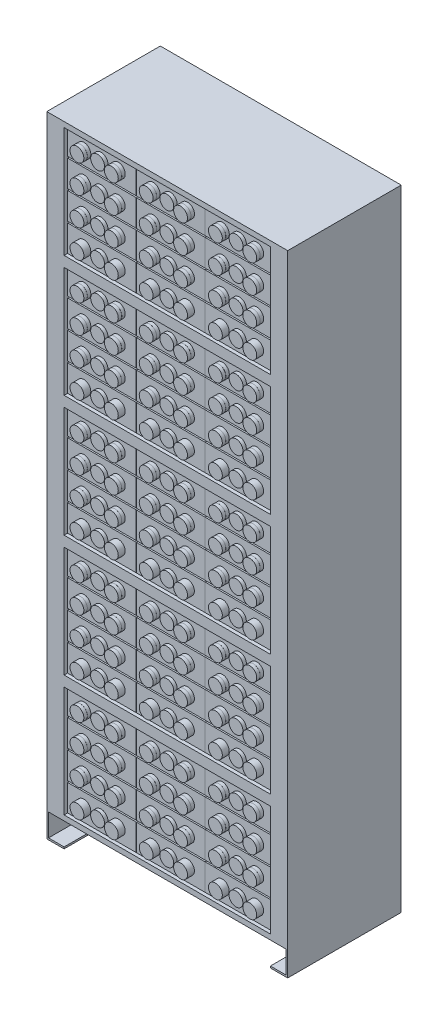
SolidWorks part; units mm, degrees
ref_plane "Front Plane" through (0, 0, 0) normal (0, 0, 1) x (1, 0, 0)
ref_plane "Top Plane" through (0, 0, 0) normal (0, 1, 0) x (1, 0, 0)
ref_plane "Right Plane" through (0, 0, 0) normal (1, 0, 0) x (0, 0, -1)
sketch "Sketch1" plane through (0, 0, 0) normal (0, 0, 1) x (1, 0, 0)
  line L0 (0, 0) -> (0, 1820)
  line L5 (0, 0) -> (50, 0)
  line L6 (696, 0) -> (696, 1820)
  line L7 (696, 1820) -> (0, 1820)
  line L8 (50, 0) -> (50, 5)
  line L10 (50, 755) -> (646, 755)
  line L11 (50, 435) -> (50, 755)
  line L12 (50, 435) -> (646, 435)
  line L14 (50, 85) -> (646, 85)
  line L15 (646, 435) -> (646, 755)
  line L16 (50, 1105) -> (646, 1105)
  line L17 (50, 85) -> (50, 405)
  line L18 (50, 405) -> (646, 405)
  line L19 (646, 85) -> (646, 405)
  line L20 (50, 785) -> (50, 1105)
  line L21 (50, 785) -> (646, 785)
  line L22 (646, 785) -> (646, 1105)
  line L23 (50, 1455) -> (646, 1455)
  line L24 (50, 1135) -> (50, 1455)
  line L25 (50, 1135) -> (646, 1135)
  line L26 (646, 1135) -> (646, 1455)
  line L27 (50, 1805) -> (646, 1805)
  line L28 (50, 1485) -> (50, 1805)
  line L29 (50, 1485) -> (646, 1485)
  line L30 (646, 1485) -> (646, 1805)
  line L31 (50, 5) -> (5, 5)
  line L32 (5, 5) -> (5, 70)
  line L33 (5, 70) -> (50, 70)
  line L34 (50, 70) -> (646, 70)
  line L36 (646, 0) -> (696, 0)
  line L37 (646, 0) -> (646, 5)
  line L39 (646, 5) -> (691, 5)
  line L40 (691, 5) -> (691, 70)
  line L41 (691, 70) -> (646, 70)
  dimension "D1" = 1820
  dimension "D2" = 696
  dimension "D3" = 320
  dimension "D4" = 5
  dimension "D5" = 596
  dimension "D6" = 15
  dimension "D7" = 15
  dimension "D8" = 70
  dimension "D9" = 5
  dimension "D10" = 5
  dimension "D11" = 596
  dimension "D12" = 45
  dimension "D13" = 65
  dimension "D14" = 5
  dimension "D15" = 45
  dimension "D16" = 50
extrude "Boss-Extrude1" add sketch "Sketch1" against normal blind 405
sketch "Sketch2" plane through (0, 0, -405) normal (0, 0, -1) x (-1, 0, 0)
  line L2 (-447.2, 161.3661) -> (-248.8, 161.3661)
  line L8 (-447.2, 511.3661) -> (-248.8, 511.3661)
  line L9 (-50, 434.5661) -> (-248.4, 434.5661)
  line L10 (-248.4, 434.5661) -> (-248.4, 511.3661)
  line L11 (-248.4, 511.3661) -> (-50, 511.3661)
  line L12 (-50, 511.3661) -> (-50, 434.5661)
  line L13 (-447.2, 434.5661) -> (-447.2, 511.3661)
  line L14 (-50, 84.5661) -> (-248.4, 84.5661)
  line L15 (-50, 405) -> (-50, 85) construction
  line L16 (-248.4, 84.5661) -> (-248.4, 161.3661)
  line L17 (-248.4, 161.3661) -> (-50, 161.3661)
  line L18 (-50, 161.3661) -> (-50, 84.5661)
  line L19 (-447.2, 84.5661) -> (-447.2, 161.3661)
  line L20 (-248.8, 84.5661) -> (-447.2, 84.5661)
  line L21 (-248.8, 161.3661) -> (-248.8, 84.5661)
  line L22 (-646, 161.3661) -> (-447.6, 161.3661)
  line L23 (-646, 84.5661) -> (-646, 161.3661)
  line L24 (-447.6, 84.5661) -> (-646, 84.5661)
  line L25 (-447.6, 161.3661) -> (-447.6, 84.5661)
  line L26 (-447.2, 242.5774) -> (-248.8, 242.5774)
  line L27 (-447.2, 165.7774) -> (-447.2, 242.5774)
  line L28 (-248.8, 165.7774) -> (-447.2, 165.7774)
  line L29 (-248.8, 242.5774) -> (-248.8, 165.7774)
  line L30 (-646, 242.5774) -> (-447.6, 242.5774)
  line L31 (-646, 165.7774) -> (-646, 242.5774)
  line L32 (-447.6, 165.7774) -> (-646, 165.7774)
  line L33 (-447.6, 242.5774) -> (-447.6, 165.7774)
  line L34 (-447.2, 323.7887) -> (-248.8, 323.7887)
  line L35 (-447.2, 246.9887) -> (-447.2, 323.7887)
  line L36 (-248.8, 246.9887) -> (-447.2, 246.9887)
  line L37 (-248.8, 323.7887) -> (-248.8, 246.9887)
  line L38 (-646, 323.7887) -> (-447.6, 323.7887)
  line L39 (-646, 246.9887) -> (-646, 323.7887)
  line L40 (-447.6, 246.9887) -> (-646, 246.9887)
  line L41 (-447.6, 323.7887) -> (-447.6, 246.9887)
  line L42 (-447.2, 405) -> (-248.8, 405)
  line L43 (-447.2, 328.2) -> (-447.2, 405)
  line L44 (-248.8, 328.2) -> (-447.2, 328.2)
  line L45 (-248.8, 405) -> (-248.8, 328.2)
  line L46 (-646, 405) -> (-447.6, 405)
  line L47 (-646, 328.2) -> (-646, 405)
  line L48 (-447.6, 328.2) -> (-646, 328.2)
  line L49 (-447.6, 405) -> (-447.6, 328.2)
  line L50 (-248.4, 242.5774) -> (-50, 242.5774)
  line L51 (-248.4, 165.7774) -> (-248.4, 242.5774)
  line L52 (-50, 165.7774) -> (-248.4, 165.7774)
  line L53 (-50, 242.5774) -> (-50, 165.7774)
  line L54 (-248.4, 323.7887) -> (-50, 323.7887)
  line L55 (-248.4, 246.9887) -> (-248.4, 323.7887)
  line L56 (-50, 246.9887) -> (-248.4, 246.9887)
  line L57 (-50, 323.7887) -> (-50, 246.9887)
  line L58 (-248.4, 405) -> (-50, 405)
  line L59 (-248.4, 328.2) -> (-248.4, 405)
  line L60 (-50, 328.2) -> (-248.4, 328.2)
  line L61 (-50, 405) -> (-50, 328.2)
  line L62 (-248.8, 434.5661) -> (-447.2, 434.5661)
  line L63 (-248.8, 511.3661) -> (-248.8, 434.5661)
  line L64 (-646, 511.3661) -> (-447.6, 511.3661)
  line L65 (-646, 434.5661) -> (-646, 511.3661)
  line L66 (-447.6, 434.5661) -> (-646, 434.5661)
  line L67 (-447.6, 511.3661) -> (-447.6, 434.5661)
  line L68 (-447.2, 592.5774) -> (-248.8, 592.5774)
  line L69 (-447.2, 515.7774) -> (-447.2, 592.5774)
  line L70 (-248.8, 515.7774) -> (-447.2, 515.7774)
  line L71 (-248.8, 592.5774) -> (-248.8, 515.7774)
  line L72 (-646, 592.5774) -> (-447.6, 592.5774)
  line L73 (-646, 515.7774) -> (-646, 592.5774)
  line L74 (-447.6, 515.7774) -> (-646, 515.7774)
  line L75 (-447.6, 592.5774) -> (-447.6, 515.7774)
  line L76 (-447.2, 673.7887) -> (-248.8, 673.7887)
  line L77 (-447.2, 596.9887) -> (-447.2, 673.7887)
  line L78 (-248.8, 596.9887) -> (-447.2, 596.9887)
  line L79 (-248.8, 673.7887) -> (-248.8, 596.9887)
  line L80 (-646, 673.7887) -> (-447.6, 673.7887)
  line L81 (-646, 596.9887) -> (-646, 673.7887)
  line L82 (-447.6, 596.9887) -> (-646, 596.9887)
  line L83 (-447.6, 673.7887) -> (-447.6, 596.9887)
  line L84 (-447.2, 755) -> (-248.8, 755)
  line L85 (-447.2, 678.2) -> (-447.2, 755)
  line L86 (-248.8, 678.2) -> (-447.2, 678.2)
  line L87 (-248.8, 755) -> (-248.8, 678.2)
  line L88 (-646, 755) -> (-447.6, 755)
  line L89 (-646, 678.2) -> (-646, 755)
  line L90 (-447.6, 678.2) -> (-646, 678.2)
  line L91 (-447.6, 755) -> (-447.6, 678.2)
  line L92 (-248.4, 592.5774) -> (-50, 592.5774)
  line L93 (-248.4, 515.7774) -> (-248.4, 592.5774)
  line L94 (-50, 515.7774) -> (-248.4, 515.7774)
  line L95 (-50, 592.5774) -> (-50, 515.7774)
  line L96 (-248.4, 673.7887) -> (-50, 673.7887)
  line L97 (-248.4, 596.9887) -> (-248.4, 673.7887)
  line L98 (-50, 596.9887) -> (-248.4, 596.9887)
  line L99 (-50, 673.7887) -> (-50, 596.9887)
  line L100 (-248.4, 755) -> (-50, 755)
  line L101 (-248.4, 678.2) -> (-248.4, 755)
  line L102 (-50, 678.2) -> (-248.4, 678.2)
  line L103 (-50, 755) -> (-50, 678.2)
  line L104 (-447.2, 861.3661) -> (-248.8, 861.3661)
  line L105 (-50, 784.5661) -> (-248.4, 784.5661)
  line L106 (-248.4, 784.5661) -> (-248.4, 861.3661)
  line L107 (-248.4, 861.3661) -> (-50, 861.3661)
  line L108 (-50, 861.3661) -> (-50, 784.5661)
  line L109 (-447.2, 784.5661) -> (-447.2, 861.3661)
  line L110 (-248.8, 784.5661) -> (-447.2, 784.5661)
  line L111 (-248.8, 861.3661) -> (-248.8, 784.5661)
  line L112 (-646, 861.3661) -> (-447.6, 861.3661)
  line L113 (-646, 784.5661) -> (-646, 861.3661)
  line L114 (-447.6, 784.5661) -> (-646, 784.5661)
  line L115 (-447.6, 861.3661) -> (-447.6, 784.5661)
  line L116 (-447.2, 942.5774) -> (-248.8, 942.5774)
  line L117 (-447.2, 865.7774) -> (-447.2, 942.5774)
  line L118 (-248.8, 865.7774) -> (-447.2, 865.7774)
  line L119 (-248.8, 942.5774) -> (-248.8, 865.7774)
  line L120 (-646, 942.5774) -> (-447.6, 942.5774)
  line L121 (-646, 865.7774) -> (-646, 942.5774)
  line L122 (-447.6, 865.7774) -> (-646, 865.7774)
  line L123 (-447.6, 942.5774) -> (-447.6, 865.7774)
  line L124 (-447.2, 1023.7887) -> (-248.8, 1023.7887)
  line L125 (-447.2, 946.9887) -> (-447.2, 1023.7887)
  line L126 (-248.8, 946.9887) -> (-447.2, 946.9887)
  line L127 (-248.8, 1023.7887) -> (-248.8, 946.9887)
  line L128 (-646, 1023.7887) -> (-447.6, 1023.7887)
  line L129 (-646, 946.9887) -> (-646, 1023.7887)
  line L130 (-447.6, 946.9887) -> (-646, 946.9887)
  line L131 (-447.6, 1023.7887) -> (-447.6, 946.9887)
  line L132 (-447.2, 1105) -> (-248.8, 1105)
  line L133 (-447.2, 1028.2) -> (-447.2, 1105)
  line L134 (-248.8, 1028.2) -> (-447.2, 1028.2)
  line L135 (-248.8, 1105) -> (-248.8, 1028.2)
  line L136 (-646, 1105) -> (-447.6, 1105)
  line L137 (-646, 1028.2) -> (-646, 1105)
  line L138 (-447.6, 1028.2) -> (-646, 1028.2)
  line L139 (-447.6, 1105) -> (-447.6, 1028.2)
  line L140 (-248.4, 942.5774) -> (-50, 942.5774)
  line L141 (-248.4, 865.7774) -> (-248.4, 942.5774)
  line L142 (-50, 865.7774) -> (-248.4, 865.7774)
  line L143 (-50, 942.5774) -> (-50, 865.7774)
  line L144 (-248.4, 1023.7887) -> (-50, 1023.7887)
  line L145 (-248.4, 946.9887) -> (-248.4, 1023.7887)
  line L146 (-50, 946.9887) -> (-248.4, 946.9887)
  line L147 (-50, 1023.7887) -> (-50, 946.9887)
  line L148 (-248.4, 1105) -> (-50, 1105)
  line L149 (-248.4, 1028.2) -> (-248.4, 1105)
  line L150 (-50, 1028.2) -> (-248.4, 1028.2)
  line L151 (-50, 1105) -> (-50, 1028.2)
  line L152 (-447.2, 1211.3661) -> (-248.8, 1211.3661)
  line L153 (-50, 1134.5661) -> (-248.4, 1134.5661)
  line L154 (-248.4, 1134.5661) -> (-248.4, 1211.3661)
  line L155 (-248.4, 1211.3661) -> (-50, 1211.3661)
  line L156 (-50, 1211.3661) -> (-50, 1134.5661)
  line L157 (-447.2, 1134.5661) -> (-447.2, 1211.3661)
  line L158 (-248.8, 1134.5661) -> (-447.2, 1134.5661)
  line L159 (-248.8, 1211.3661) -> (-248.8, 1134.5661)
  line L160 (-646, 1211.3661) -> (-447.6, 1211.3661)
  line L161 (-646, 1134.5661) -> (-646, 1211.3661)
  line L162 (-447.6, 1134.5661) -> (-646, 1134.5661)
  line L163 (-447.6, 1211.3661) -> (-447.6, 1134.5661)
  line L164 (-447.2, 1292.5774) -> (-248.8, 1292.5774)
  line L165 (-447.2, 1215.7774) -> (-447.2, 1292.5774)
  line L166 (-248.8, 1215.7774) -> (-447.2, 1215.7774)
  line L167 (-248.8, 1292.5774) -> (-248.8, 1215.7774)
  line L168 (-646, 1292.5774) -> (-447.6, 1292.5774)
  line L169 (-646, 1215.7774) -> (-646, 1292.5774)
  line L170 (-447.6, 1215.7774) -> (-646, 1215.7774)
  line L171 (-447.6, 1292.5774) -> (-447.6, 1215.7774)
  line L172 (-447.2, 1373.7887) -> (-248.8, 1373.7887)
  line L173 (-447.2, 1296.9887) -> (-447.2, 1373.7887)
  line L174 (-248.8, 1296.9887) -> (-447.2, 1296.9887)
  line L175 (-248.8, 1373.7887) -> (-248.8, 1296.9887)
  line L176 (-646, 1373.7887) -> (-447.6, 1373.7887)
  line L177 (-646, 1296.9887) -> (-646, 1373.7887)
  line L178 (-447.6, 1296.9887) -> (-646, 1296.9887)
  line L179 (-447.6, 1373.7887) -> (-447.6, 1296.9887)
  line L180 (-447.2, 1455) -> (-248.8, 1455)
  line L181 (-447.2, 1378.2) -> (-447.2, 1455)
  line L182 (-248.8, 1378.2) -> (-447.2, 1378.2)
  line L183 (-248.8, 1455) -> (-248.8, 1378.2)
  line L184 (-646, 1455) -> (-447.6, 1455)
  line L185 (-646, 1378.2) -> (-646, 1455)
  line L186 (-447.6, 1378.2) -> (-646, 1378.2)
  line L187 (-447.6, 1455) -> (-447.6, 1378.2)
  line L188 (-248.4, 1292.5774) -> (-50, 1292.5774)
  line L189 (-248.4, 1215.7774) -> (-248.4, 1292.5774)
  line L190 (-50, 1215.7774) -> (-248.4, 1215.7774)
  line L191 (-50, 1292.5774) -> (-50, 1215.7774)
  line L192 (-248.4, 1373.7887) -> (-50, 1373.7887)
  line L193 (-248.4, 1296.9887) -> (-248.4, 1373.7887)
  line L194 (-50, 1296.9887) -> (-248.4, 1296.9887)
  line L195 (-50, 1373.7887) -> (-50, 1296.9887)
  line L196 (-248.4, 1455) -> (-50, 1455)
  line L197 (-248.4, 1378.2) -> (-248.4, 1455)
  line L198 (-50, 1378.2) -> (-248.4, 1378.2)
  line L199 (-50, 1455) -> (-50, 1378.2)
  line L200 (-447.2, 1561.3661) -> (-248.8, 1561.3661)
  line L201 (-50, 1484.5661) -> (-248.4, 1484.5661)
  line L202 (-248.4, 1484.5661) -> (-248.4, 1561.3661)
  line L203 (-248.4, 1561.3661) -> (-50, 1561.3661)
  line L204 (-50, 1561.3661) -> (-50, 1484.5661)
  line L205 (-447.2, 1484.5661) -> (-447.2, 1561.3661)
  line L206 (-248.8, 1484.5661) -> (-447.2, 1484.5661)
  line L207 (-248.8, 1561.3661) -> (-248.8, 1484.5661)
  line L208 (-646, 1561.3661) -> (-447.6, 1561.3661)
  line L209 (-646, 1484.5661) -> (-646, 1561.3661)
  line L210 (-447.6, 1484.5661) -> (-646, 1484.5661)
  line L211 (-447.6, 1561.3661) -> (-447.6, 1484.5661)
  line L212 (-447.2, 1642.5774) -> (-248.8, 1642.5774)
  line L213 (-447.2, 1565.7774) -> (-447.2, 1642.5774)
  line L214 (-248.8, 1565.7774) -> (-447.2, 1565.7774)
  line L215 (-248.8, 1642.5774) -> (-248.8, 1565.7774)
  line L216 (-646, 1642.5774) -> (-447.6, 1642.5774)
  line L217 (-646, 1565.7774) -> (-646, 1642.5774)
  line L218 (-447.6, 1565.7774) -> (-646, 1565.7774)
  line L219 (-447.6, 1642.5774) -> (-447.6, 1565.7774)
  line L220 (-447.2, 1723.7887) -> (-248.8, 1723.7887)
  line L221 (-447.2, 1646.9887) -> (-447.2, 1723.7887)
  line L222 (-248.8, 1646.9887) -> (-447.2, 1646.9887)
  line L223 (-248.8, 1723.7887) -> (-248.8, 1646.9887)
  line L224 (-646, 1723.7887) -> (-447.6, 1723.7887)
  line L225 (-646, 1646.9887) -> (-646, 1723.7887)
  line L226 (-447.6, 1646.9887) -> (-646, 1646.9887)
  line L227 (-447.6, 1723.7887) -> (-447.6, 1646.9887)
  line L228 (-447.2, 1805) -> (-248.8, 1805)
  line L229 (-447.2, 1728.2) -> (-447.2, 1805)
  line L230 (-248.8, 1728.2) -> (-447.2, 1728.2)
  line L231 (-248.8, 1805) -> (-248.8, 1728.2)
  line L232 (-646, 1805) -> (-447.6, 1805)
  line L233 (-646, 1728.2) -> (-646, 1805)
  line L234 (-447.6, 1728.2) -> (-646, 1728.2)
  line L235 (-447.6, 1805) -> (-447.6, 1728.2)
  line L236 (-248.4, 1642.5774) -> (-50, 1642.5774)
  line L237 (-248.4, 1565.7774) -> (-248.4, 1642.5774)
  line L238 (-50, 1565.7774) -> (-248.4, 1565.7774)
  line L239 (-50, 1642.5774) -> (-50, 1565.7774)
  line L240 (-248.4, 1723.7887) -> (-50, 1723.7887)
  line L241 (-248.4, 1646.9887) -> (-248.4, 1723.7887)
  line L242 (-50, 1646.9887) -> (-248.4, 1646.9887)
  line L243 (-50, 1723.7887) -> (-50, 1646.9887)
  line L244 (-248.4, 1805) -> (-50, 1805)
  line L245 (-248.4, 1728.2) -> (-248.4, 1805)
  line L246 (-50, 1728.2) -> (-248.4, 1728.2)
  line L247 (-50, 1805) -> (-50, 1728.2)
  line L248 (-646, 1805) -> (-50, 1805) construction
  dimension "D1" = 198.4
  dimension "D2" = 3
  dimension "D4" = 5
  dimension "D5" = 76.8
  dimension "D3" = 4
extrude "Boss-Extrude2" add sketch "Sketch2" against normal blind 318
sketch "Sketch3" plane through (0, 0, -87) normal (0, 0, 1) x (1, 0, 0)
  line L0 (447.6, 85) -> (447.6, 161.3661) construction
  line L1 (526.6, 123.183) -> (566.6, 123.183) construction
  line L2 (546.8, 161.3661) -> (546.8, 85) construction
  line L3 (646, 85) -> (447.6, 85) construction
  line L4 (447.6, 85) -> (447.6, 161.3661) construction
  line L5 (546.6, 123.183) -> (447.6, 123.183) construction
  line L6 (447.6, 1805) -> (646, 1805) construction
  line L7 (447.6, 1805) -> (646, 1805) construction
  line L8 (546.8, 405) -> (546.8, 328.2) construction
  line L9 (646, 328.2) -> (447.6, 328.2) construction
  line L10 (546.8, 1805) -> (546.8, 1728.2) construction
  line L11 (646, 1728.2) -> (447.6, 1728.2) construction
  line L12 (646, 1766.6) -> (447.6, 1766.6) construction
  line L13 (646, 1805) -> (646, 1728.2) construction
  line L14 (447.6, 1728.2) -> (447.6, 1805) construction
  circle A0 centre (546.6, 123.183) radius 20
  circle A1 centre (497.1, 123.183) radius 20
  circle A2 centre (596.5, 123.183) radius 20
  circle A3 centre (297.1, 123.183) radius 20
  circle A4 centre (346.6, 123.183) radius 20
  circle A5 centre (396.5, 123.183) radius 20
  circle A6 centre (97.1, 123.183) radius 20
  circle A7 centre (146.6, 123.183) radius 20
  circle A8 centre (196.5, 123.183) radius 20
  circle A9 centre (297.1667, 204.322) radius 20
  circle A10 centre (346.6667, 204.322) radius 20
  circle A11 centre (396.5667, 204.322) radius 20
  circle A12 centre (97.1667, 204.322) radius 20
  circle A13 centre (146.6667, 204.322) radius 20
  circle A14 centre (196.5667, 204.322) radius 20
  circle A15 centre (297.2333, 285.461) radius 20
  circle A16 centre (346.7333, 285.461) radius 20
  circle A17 centre (396.6333, 285.461) radius 20
  circle A18 centre (97.2333, 285.461) radius 20
  circle A19 centre (146.7333, 285.461) radius 20
  circle A20 centre (196.6333, 285.461) radius 20
  circle A21 centre (297.3, 366.6) radius 20
  circle A22 centre (346.8, 366.6) radius 20
  circle A23 centre (396.7, 366.6) radius 20
  circle A24 centre (97.3, 366.6) radius 20
  circle A25 centre (146.8, 366.6) radius 20
  circle A26 centre (196.7, 366.6) radius 20
  circle A27 centre (497.1667, 204.322) radius 20
  circle A28 centre (546.6667, 204.322) radius 20
  circle A29 centre (596.5667, 204.322) radius 20
  circle A30 centre (497.2333, 285.461) radius 20
  circle A31 centre (546.7333, 285.461) radius 20
  circle A32 centre (596.6333, 285.461) radius 20
  circle A33 centre (497.3, 366.6) radius 20
  circle A34 centre (546.8, 366.6) radius 20
  circle A35 centre (596.7, 366.6) radius 20
  circle A36 centre (546.6, 473.183) radius 20
  circle A37 centre (497.1, 473.183) radius 20
  circle A38 centre (596.5, 473.183) radius 20
  circle A39 centre (297.1, 473.183) radius 20
  circle A40 centre (346.6, 473.183) radius 20
  circle A41 centre (396.5, 473.183) radius 20
  circle A42 centre (97.1, 473.183) radius 20
  circle A43 centre (146.6, 473.183) radius 20
  circle A44 centre (196.5, 473.183) radius 20
  circle A45 centre (297.1667, 554.322) radius 20
  circle A46 centre (346.6667, 554.322) radius 20
  circle A47 centre (396.5667, 554.322) radius 20
  circle A48 centre (97.1667, 554.322) radius 20
  circle A49 centre (146.6667, 554.322) radius 20
  circle A50 centre (196.5667, 554.322) radius 20
  circle A51 centre (297.2333, 635.461) radius 20
  circle A52 centre (346.7333, 635.461) radius 20
  circle A53 centre (396.6333, 635.461) radius 20
  circle A54 centre (97.2333, 635.461) radius 20
  circle A55 centre (146.7333, 635.461) radius 20
  circle A56 centre (196.6333, 635.461) radius 20
  circle A57 centre (297.3, 716.6) radius 20
  circle A58 centre (346.8, 716.6) radius 20
  circle A59 centre (396.7, 716.6) radius 20
  circle A60 centre (97.3, 716.6) radius 20
  circle A61 centre (146.8, 716.6) radius 20
  circle A62 centre (196.7, 716.6) radius 20
  circle A63 centre (497.1667, 554.322) radius 20
  circle A64 centre (546.6667, 554.322) radius 20
  circle A65 centre (596.5667, 554.322) radius 20
  circle A66 centre (497.2333, 635.461) radius 20
  circle A67 centre (546.7333, 635.461) radius 20
  circle A68 centre (596.6333, 635.461) radius 20
  circle A69 centre (497.3, 716.6) radius 20
  circle A70 centre (546.8, 716.6) radius 20
  circle A71 centre (596.7, 716.6) radius 20
  circle A72 centre (546.6, 823.183) radius 20
  circle A73 centre (497.1, 823.183) radius 20
  circle A74 centre (596.5, 823.183) radius 20
  circle A75 centre (297.1, 823.183) radius 20
  circle A76 centre (346.6, 823.183) radius 20
  circle A77 centre (396.5, 823.183) radius 20
  circle A78 centre (97.1, 823.183) radius 20
  circle A79 centre (146.6, 823.183) radius 20
  circle A80 centre (196.5, 823.183) radius 20
  circle A81 centre (297.1667, 904.322) radius 20
  circle A82 centre (346.6667, 904.322) radius 20
  circle A83 centre (396.5667, 904.322) radius 20
  circle A84 centre (97.1667, 904.322) radius 20
  circle A85 centre (146.6667, 904.322) radius 20
  circle A86 centre (196.5667, 904.322) radius 20
  circle A87 centre (297.2333, 985.461) radius 20
  circle A88 centre (346.7333, 985.461) radius 20
  circle A89 centre (396.6333, 985.461) radius 20
  circle A90 centre (97.2333, 985.461) radius 20
  circle A91 centre (146.7333, 985.461) radius 20
  circle A92 centre (196.6333, 985.461) radius 20
  circle A93 centre (297.3, 1066.6) radius 20
  circle A94 centre (346.8, 1066.6) radius 20
  circle A95 centre (396.7, 1066.6) radius 20
  circle A96 centre (97.3, 1066.6) radius 20
  circle A97 centre (146.8, 1066.6) radius 20
  circle A98 centre (196.7, 1066.6) radius 20
  circle A99 centre (497.1667, 904.322) radius 20
  circle A100 centre (546.6667, 904.322) radius 20
  circle A101 centre (596.5667, 904.322) radius 20
  circle A102 centre (497.2333, 985.461) radius 20
  circle A103 centre (546.7333, 985.461) radius 20
  circle A104 centre (596.6333, 985.461) radius 20
  circle A105 centre (497.3, 1066.6) radius 20
  circle A106 centre (546.8, 1066.6) radius 20
  circle A107 centre (596.7, 1066.6) radius 20
  circle A108 centre (546.6, 1173.183) radius 20
  circle A109 centre (497.1, 1173.183) radius 20
  circle A110 centre (596.5, 1173.183) radius 20
  circle A111 centre (297.1, 1173.183) radius 20
  circle A112 centre (346.6, 1173.183) radius 20
  circle A113 centre (396.5, 1173.183) radius 20
  circle A114 centre (97.1, 1173.183) radius 20
  circle A115 centre (146.6, 1173.183) radius 20
  circle A116 centre (196.5, 1173.183) radius 20
  circle A117 centre (297.1667, 1254.322) radius 20
  circle A118 centre (346.6667, 1254.322) radius 20
  circle A119 centre (396.5667, 1254.322) radius 20
  circle A120 centre (97.1667, 1254.322) radius 20
  circle A121 centre (146.6667, 1254.322) radius 20
  circle A122 centre (196.5667, 1254.322) radius 20
  circle A123 centre (297.2333, 1335.461) radius 20
  circle A124 centre (346.7333, 1335.461) radius 20
  circle A125 centre (396.6333, 1335.461) radius 20
  circle A126 centre (97.2333, 1335.461) radius 20
  circle A127 centre (146.7333, 1335.461) radius 20
  circle A128 centre (196.6333, 1335.461) radius 20
  circle A129 centre (297.3, 1416.6) radius 20
  circle A130 centre (346.8, 1416.6) radius 20
  circle A131 centre (396.7, 1416.6) radius 20
  circle A132 centre (97.3, 1416.6) radius 20
  circle A133 centre (146.8, 1416.6) radius 20
  circle A134 centre (196.7, 1416.6) radius 20
  circle A135 centre (497.1667, 1254.322) radius 20
  circle A136 centre (546.6667, 1254.322) radius 20
  circle A137 centre (596.5667, 1254.322) radius 20
  circle A138 centre (497.2333, 1335.461) radius 20
  circle A139 centre (546.7333, 1335.461) radius 20
  circle A140 centre (596.6333, 1335.461) radius 20
  circle A141 centre (497.3, 1416.6) radius 20
  circle A142 centre (546.8, 1416.6) radius 20
  circle A143 centre (596.7, 1416.6) radius 20
  circle A144 centre (546.6, 1523.183) radius 20
  circle A145 centre (497.1, 1523.183) radius 20
  circle A146 centre (596.5, 1523.183) radius 20
  circle A147 centre (297.1, 1523.183) radius 20
  circle A148 centre (346.6, 1523.183) radius 20
  circle A149 centre (396.5, 1523.183) radius 20
  circle A150 centre (97.1, 1523.183) radius 20
  circle A151 centre (146.6, 1523.183) radius 20
  circle A152 centre (196.5, 1523.183) radius 20
  circle A153 centre (297.1667, 1604.322) radius 20
  circle A154 centre (346.6667, 1604.322) radius 20
  circle A155 centre (396.5667, 1604.322) radius 20
  circle A156 centre (97.1667, 1604.322) radius 20
  circle A157 centre (146.6667, 1604.322) radius 20
  circle A158 centre (196.5667, 1604.322) radius 20
  circle A159 centre (297.2333, 1685.461) radius 20
  circle A160 centre (346.7333, 1685.461) radius 20
  circle A161 centre (396.6333, 1685.461) radius 20
  circle A162 centre (97.2333, 1685.461) radius 20
  circle A163 centre (146.7333, 1685.461) radius 20
  circle A164 centre (196.6333, 1685.461) radius 20
  circle A165 centre (297.3, 1766.6) radius 20
  circle A166 centre (346.8, 1766.6) radius 20
  circle A167 centre (396.7, 1766.6) radius 20
  circle A168 centre (97.3, 1766.6) radius 20
  circle A169 centre (146.8, 1766.6) radius 20
  circle A170 centre (196.7, 1766.6) radius 20
  circle A171 centre (497.1667, 1604.322) radius 20
  circle A172 centre (546.6667, 1604.322) radius 20
  circle A173 centre (596.5667, 1604.322) radius 20
  circle A174 centre (497.2333, 1685.461) radius 20
  circle A175 centre (546.7333, 1685.461) radius 20
  circle A176 centre (596.6333, 1685.461) radius 20
  circle A177 centre (497.3, 1766.6) radius 20
  circle A178 centre (546.8, 1766.6) radius 20
  circle A179 centre (596.7, 1766.6) radius 20
  point P388 (546.8, 1766.6)
  dimension "D1" = 40
  dimension "D2" = 40
  dimension "D5" = 5
  dimension "D3" = 3
  dimension "D4" = 4
extrude "Boss-Extrude3" add sketch "Sketch3" along normal blind 10
sketch "Sketch4" plane through (0, 0, 0) normal (0, 0, 1) x (1, 0, 0)
  line L12 (0, 0) -> (50, 0)
  line L13 (50, 0) -> (50, 5)
  line L14 (50, 5) -> (5, 5)
  line L15 (5, 5) -> (5, 70)
  line L16 (5, 70) -> (691, 70)
  line L17 (691, 70) -> (691, 5)
  line L18 (691, 5) -> (646, 5)
  line L19 (646, 5) -> (646, 0)
  line L20 (646, 0) -> (696, 0)
  line L21 (696, 0) -> (696, 1820)
  line L22 (696, 1820) -> (0, 1820)
  line L23 (0, 1820) -> (0, 0)
  line L24 (0, 0) -> (50, 0)
  line L25 (50, 0) -> (50, 5)
  line L26 (50, 5) -> (5, 5)
  line L27 (5, 5) -> (5, 70)
  line L28 (5, 70) -> (691, 70)
  line L29 (691, 70) -> (691, 5)
  line L30 (691, 5) -> (646, 5)
  line L31 (646, 5) -> (646, 0)
  line L32 (646, 0) -> (696, 0)
  line L33 (696, 0) -> (696, 1820)
  line L34 (696, 1820) -> (0, 1820)
  line L35 (0, 1820) -> (0, 0)
  dimension "D1" = 0
extrude "Cut-Extrude1" cut sketch "Sketch4" against normal up to surface (77 mm away) up to face at (317.1667, 1604.322, -77)
sketch "Sketch5" plane through (0, 0, -77) normal (0, 0, 1) x (1, 0, 0)
  circle A0 centre (596.5, 123.183) radius 20 construction
  circle A1 centre (596.5, 123.183) radius 20
  circle A2 centre (497.1, 123.183) radius 20 construction
  circle A3 centre (497.1, 123.183) radius 20
  circle A4 centre (297.1, 123.183) radius 20 construction
  circle A5 centre (297.1, 123.183) radius 20
  circle A6 centre (196.5, 123.183) radius 20 construction
  circle A7 centre (97.1, 123.183) radius 20 construction
  circle A8 centre (396.5, 123.183) radius 20 construction
  circle A9 centre (196.5, 123.183) radius 20
  circle A10 centre (97.1, 123.183) radius 20
  circle A11 centre (396.5, 123.183) radius 20
  circle A12 centre (97.1, 204.322) radius 20
  circle A13 centre (196.5, 204.322) radius 20
  circle A14 centre (297.1, 204.322) radius 20
  circle A15 centre (396.5, 204.322) radius 20
  circle A16 centre (497.1, 204.322) radius 20
  circle A17 centre (596.5, 204.322) radius 20
  circle A18 centre (97.1, 285.461) radius 20
  circle A19 centre (196.5, 285.461) radius 20
  circle A20 centre (297.1, 285.461) radius 20
  circle A21 centre (396.5, 285.461) radius 20
  circle A22 centre (497.1, 285.461) radius 20
  circle A23 centre (596.5, 285.461) radius 20
  circle A24 centre (97.1, 366.6) radius 20
  circle A25 centre (196.5, 366.6) radius 20
  circle A26 centre (297.1, 366.6) radius 20
  circle A27 centre (396.5, 366.6) radius 20
  circle A28 centre (497.1, 366.6) radius 20
  circle A29 centre (596.5, 366.6) radius 20
  circle A31 centre (596.5, 473.183) radius 20
  circle A32 centre (497.1, 473.183) radius 20
  circle A33 centre (297.1, 473.183) radius 20
  circle A34 centre (196.5, 473.183) radius 20
  circle A35 centre (97.1, 473.183) radius 20
  circle A36 centre (396.5, 473.183) radius 20
  circle A37 centre (97.1, 554.322) radius 20
  circle A38 centre (196.5, 554.322) radius 20
  circle A39 centre (297.1, 554.322) radius 20
  circle A40 centre (396.5, 554.322) radius 20
  circle A41 centre (497.1, 554.322) radius 20
  circle A42 centre (596.5, 554.322) radius 20
  circle A43 centre (97.1, 635.461) radius 20
  circle A44 centre (196.5, 635.461) radius 20
  circle A45 centre (297.1, 635.461) radius 20
  circle A46 centre (396.5, 635.461) radius 20
  circle A47 centre (497.1, 635.461) radius 20
  circle A48 centre (596.5, 635.461) radius 20
  circle A49 centre (97.1, 716.6) radius 20
  circle A50 centre (196.5, 716.6) radius 20
  circle A51 centre (297.1, 716.6) radius 20
  circle A52 centre (396.5, 716.6) radius 20
  circle A53 centre (497.1, 716.6) radius 20
  circle A54 centre (596.5, 716.6) radius 20
  circle A55 centre (596.5, 823.183) radius 20
  circle A56 centre (497.1, 823.183) radius 20
  circle A57 centre (297.1, 823.183) radius 20
  circle A58 centre (196.5, 823.183) radius 20
  circle A59 centre (97.1, 823.183) radius 20
  circle A60 centre (396.5, 823.183) radius 20
  circle A61 centre (97.1, 904.322) radius 20
  circle A62 centre (196.5, 904.322) radius 20
  circle A63 centre (297.1, 904.322) radius 20
  circle A64 centre (396.5, 904.322) radius 20
  circle A65 centre (497.1, 904.322) radius 20
  circle A66 centre (596.5, 904.322) radius 20
  circle A67 centre (97.1, 985.461) radius 20
  circle A68 centre (196.5, 985.461) radius 20
  circle A69 centre (297.1, 985.461) radius 20
  circle A70 centre (396.5, 985.461) radius 20
  circle A71 centre (497.1, 985.461) radius 20
  circle A72 centre (596.5, 985.461) radius 20
  circle A73 centre (97.1, 1066.6) radius 20
  circle A74 centre (196.5, 1066.6) radius 20
  circle A75 centre (297.1, 1066.6) radius 20
  circle A76 centre (396.5, 1066.6) radius 20
  circle A77 centre (497.1, 1066.6) radius 20
  circle A78 centre (596.5, 1066.6) radius 20
  circle A79 centre (596.5, 1173.183) radius 20
  circle A80 centre (497.1, 1173.183) radius 20
  circle A81 centre (297.1, 1173.183) radius 20
  circle A82 centre (196.5, 1173.183) radius 20
  circle A83 centre (97.1, 1173.183) radius 20
  circle A84 centre (396.5, 1173.183) radius 20
  circle A85 centre (97.1, 1254.322) radius 20
  circle A86 centre (196.5, 1254.322) radius 20
  circle A87 centre (297.1, 1254.322) radius 20
  circle A88 centre (396.5, 1254.322) radius 20
  circle A89 centre (497.1, 1254.322) radius 20
  circle A90 centre (596.5, 1254.322) radius 20
  circle A91 centre (97.1, 1335.461) radius 20
  circle A92 centre (196.5, 1335.461) radius 20
  circle A93 centre (297.1, 1335.461) radius 20
  circle A94 centre (396.5, 1335.461) radius 20
  circle A95 centre (497.1, 1335.461) radius 20
  circle A96 centre (596.5, 1335.461) radius 20
  circle A97 centre (97.1, 1416.6) radius 20
  circle A98 centre (196.5, 1416.6) radius 20
  circle A99 centre (297.1, 1416.6) radius 20
  circle A100 centre (396.5, 1416.6) radius 20
  circle A101 centre (497.1, 1416.6) radius 20
  circle A102 centre (596.5, 1416.6) radius 20
  circle A103 centre (596.5, 1523.183) radius 20
  circle A104 centre (497.1, 1523.183) radius 20
  circle A105 centre (297.1, 1523.183) radius 20
  circle A106 centre (196.5, 1523.183) radius 20
  circle A107 centre (97.1, 1523.183) radius 20
  circle A108 centre (396.5, 1523.183) radius 20
  circle A109 centre (97.1, 1604.322) radius 20
  circle A110 centre (196.5, 1604.322) radius 20
  circle A111 centre (297.1, 1604.322) radius 20
  circle A112 centre (396.5, 1604.322) radius 20
  circle A113 centre (497.1, 1604.322) radius 20
  circle A114 centre (596.5, 1604.322) radius 20
  circle A115 centre (97.1, 1685.461) radius 20
  circle A116 centre (196.5, 1685.461) radius 20
  circle A117 centre (297.1, 1685.461) radius 20
  circle A118 centre (396.5, 1685.461) radius 20
  circle A119 centre (497.1, 1685.461) radius 20
  circle A120 centre (596.5, 1685.461) radius 20
  circle A121 centre (97.1, 1766.6) radius 20
  circle A122 centre (196.5, 1766.6) radius 20
  circle A123 centre (297.1, 1766.6) radius 20
  circle A124 centre (396.5, 1766.6) radius 20
  circle A125 centre (497.1, 1766.6) radius 20
  circle A126 centre (596.5, 1766.6) radius 20
  point P18 (97.1, 463.2176)
  point P56 (0, 0)
  point P248 (97.3, 1766.6)
  point P250 (0, 0)
  dimension "D1" = 4
  dimension "D2" = 5
extrude "Boss-Extrude5" add sketch "Sketch5" along normal blind 10
